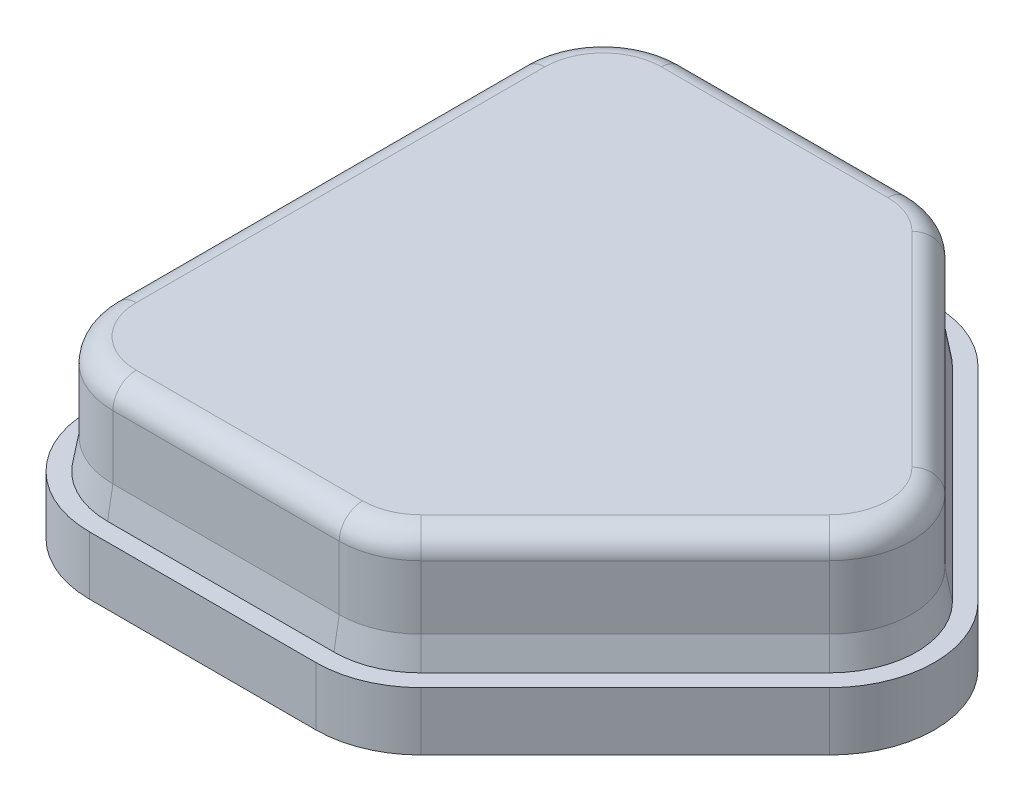
SolidWorks part; units mm, degrees
ref_plane "前视基准面" through (0, 0, 0) normal (0, 0, 1) x (1, 0, 0)
ref_plane "上视基准面" through (0, 0, 0) normal (0, 1, 0) x (1, 0, 0)
ref_plane "右视基准面" through (0, 0, 0) normal (1, 0, 0) x (0, 0, -1)
sketch "草图1" plane through (0, 0, 0) normal (0, 1, 0) x (1, 0, 0)
  line L0 (0, 0) -> (5, 0) construction
  line L1 (-6, 5) -> (0, 5) construction
  line L2 (-6, 5) -> (-6, -5) construction
  line L3 (-6, -5) -> (0, -5) construction
  line L4 (0, 5) -> (0, -5) construction
  line L5 (0, 0) -> (0, 5) construction
  line L6 (0.4393, -4.5607) -> (3.9393, -1.0607)
  line L7 (-6, 3.5) -> (-6, -3.5)
  line L8 (-4.5, -5) -> (-0.6213, -5)
  line L9 (3.9393, 1.0607) -> (0.4393, 4.5607)
  line L10 (-0.6213, 5) -> (-4.5, 5)
  line L11 (5, 0) -> (5.5, 0) construction
  arc A0 (-0.6213, -5) -> (0.4393, -4.5607) centre (-0.6213, -3.5) ccw
  arc A1 (0.4393, 4.5607) -> (-0.6213, 5) centre (-0.6213, 3.5) ccw
  arc A2 (-6, -3.5) -> (-4.5, -5) centre (-4.5, -3.5) ccw
  arc A3 (3.9393, -1.0607) -> (3.9393, 1.0607) centre (2.8787, 0) ccw
  arc A4 (-4.5, 5) -> (-6, 3.5) centre (-4.5, 3.5) ccw
  dimension "D4" = 1.5
  dimension "D5" = 1.5
  dimension "D6" = 1.5
  dimension "D7" = 1.5
  dimension "D8" = 1.5
  dimension "D1" = 10
  dimension "D2" = 6
  dimension "D3" = 5
  dimension "D9" = 5.5
sketch "草图5" plane through (0, 0, 0) normal (0, 1, 0) x (1, 0, 0)
  line L5 (-4.5, -5.3) -> (-0.6213, -5.3)
  line L6 (0.6515, -4.7728) -> (4.1515, -1.2728)
  line L7 (4.1515, 1.2728) -> (0.6515, 4.7728)
  line L8 (-0.6213, 5.3) -> (-4.5, 5.3)
  line L9 (-6.3, 3.5) -> (-6.3, -3.5)
  line L10 (-4.5, -5.3) -> (-0.6213, -5.3)
  line L11 (0.6515, -4.7728) -> (4.1515, -1.2728)
  line L12 (4.1515, 1.2728) -> (0.6515, 4.7728)
  line L13 (-0.6213, 5.3) -> (-4.5, 5.3)
  line L14 (-6.3, 3.5) -> (-6.3, -3.5)
  arc A5 (-0.6213, -5.3) -> (0.6515, -4.7728) centre (-0.6213, -3.5) ccw
  arc A6 (4.1515, -1.2728) -> (4.1515, 1.2728) centre (2.8787, 0) ccw
  arc A7 (0.6515, 4.7728) -> (-0.6213, 5.3) centre (-0.6213, 3.5) ccw
  arc A8 (-4.5, 5.3) -> (-6.3, 3.5) centre (-4.5, 3.5) ccw
  arc A9 (-6.3, -3.5) -> (-4.5, -5.3) centre (-4.5, -3.5) ccw
  arc A10 (-0.6213, -5.3) -> (0.6515, -4.7728) centre (-0.6213, -3.5) ccw
  arc A11 (4.1515, -1.2728) -> (4.1515, 1.2728) centre (2.8787, 0) ccw
  arc A12 (0.6515, 4.7728) -> (-0.6213, 5.3) centre (-0.6213, 3.5) ccw
  arc A13 (-4.5, 5.3) -> (-6.3, 3.5) centre (-4.5, 3.5) ccw
  arc A14 (-6.3, -3.5) -> (-4.5, -5.3) centre (-4.5, -3.5) ccw
  dimension "D1" = 0.3
extrude "凸台-拉伸3" add sketch "草图5" along normal blind 1
sketch "草图6" plane through (0, 1, 0) normal (0, 1, 0) x (1, 0, 0)
  line L10 (-4.5, -4.9) -> (-0.6213, -4.9)
  line L11 (0.3686, -4.4899) -> (3.8686, -0.9899)
  line L12 (3.8686, 0.9899) -> (0.3686, 4.4899)
  line L13 (-0.6213, 4.9) -> (-4.5, 4.9)
  line L14 (-5.9, 3.5) -> (-5.9, -3.5)
  line L15 (-4.5, -4.9) -> (-0.6213, -4.9)
  line L16 (0.3686, -4.4899) -> (3.8686, -0.9899)
  line L17 (3.8686, 0.9899) -> (0.3686, 4.4899)
  line L18 (-0.6213, 4.9) -> (-4.5, 4.9)
  line L19 (-5.9, 3.5) -> (-5.9, -3.5)
  arc A10 (-0.6213, -4.9) -> (0.3686, -4.4899) centre (-0.6213, -3.5) ccw
  arc A11 (3.8686, -0.9899) -> (3.8686, 0.9899) centre (2.8787, 0) ccw
  arc A12 (0.3686, 4.4899) -> (-0.6213, 4.9) centre (-0.6213, 3.5) ccw
  arc A13 (-4.5, 4.9) -> (-5.9, 3.5) centre (-4.5, 3.5) ccw
  arc A14 (-5.9, -3.5) -> (-4.5, -4.9) centre (-4.5, -3.5) ccw
  arc A15 (-0.6213, -4.9) -> (0.3686, -4.4899) centre (-0.6213, -3.5) ccw
  arc A16 (3.8686, -0.9899) -> (3.8686, 0.9899) centre (2.8787, 0) ccw
  arc A17 (0.3686, 4.4899) -> (-0.6213, 4.9) centre (-0.6213, 3.5) ccw
  arc A18 (-4.5, 4.9) -> (-5.9, 3.5) centre (-4.5, 3.5) ccw
  arc A19 (-5.9, -3.5) -> (-4.5, -4.9) centre (-4.5, -3.5) ccw
  dimension "D1" = 0.1
extrude "凸台-拉伸4" add sketch "草图6" along normal blind 2
chamfer "倒角1" distance 0.09 angle 80 10 edges at (-0.0856, 1, -4.7934) (-2.5607, 1, -4.9) (2.1186, 1, -2.7399) (-5.4899, 1, -4.4899) (4.2787, 1, 0) (-5.9, 1, 0) (2.1186, 1, 2.7399) (-5.4899, 1, 4.4899) (-0.0856, 1, 4.7934) (-2.5607, 1, 4.9) first distance on face at (-1.3656, 1, 0)
fillet "圆角3" radius 0.4 10 edges at (-5.9, 3, 0) (-5.4899, 3, -4.4899) (-2.5607, 3, -4.9) (-0.0856, 3, -4.7934) (2.1186, 3, -2.7399) (4.2787, 3, 0) (2.1186, 3, 2.7399) (-0.0856, 3, 4.7934) (-2.5607, 3, 4.9) (-5.4899, 3, 4.4899)
ref_axis "中心轴" through (0, 2.8504, 0) along (0, -1, 0)
sketch "草图7" plane through (0, 3, 0) normal (0, 1, 0) x (1, 0, 0)
  point P0 (-1.6, 0)
  dimension "D1" = 1.6
ref_axis "重心" through (-1.6, -0.4258, 0) along (0, 1, 0)
sketch "草图8" plane through (0, 0, 0) normal (0, -1, 0) x (1, 0, 0)
  circle A0 centre (-1.6, 0) radius 1.65
  dimension "D1" = 3.3
extrude "切除-拉伸1" cut sketch "草图8" against normal offset from surface (1.65 mm away) 1.35 up to face at (-1.3963, 3, 0)
